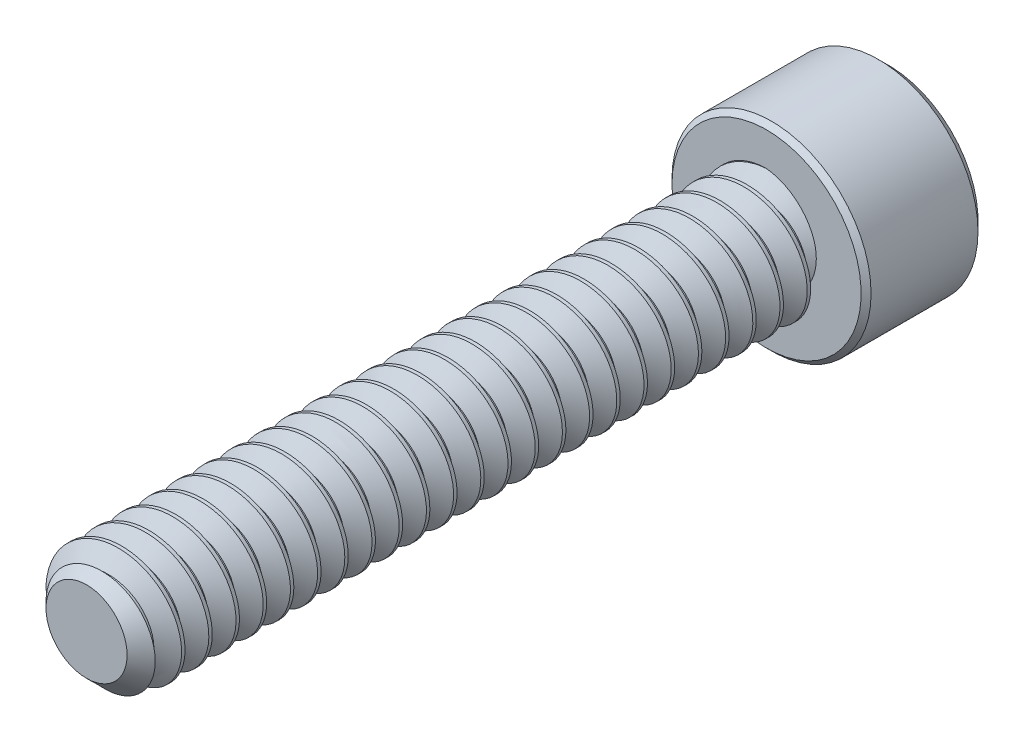
SolidWorks part; units mm, degrees
ref_plane "Front Plane" through (0, 0, 0) normal (0, 0, 1) x (1, 0, 0)
ref_plane "Top Plane" through (0, 0, 0) normal (0, 1, 0) x (1, 0, 0)
ref_plane "Right Plane" through (0, 0, 0) normal (1, 0, 0) x (0, 0, -1)
sketch "Sketch0" plane through (0, 0, 0) normal (1, 0, 0) x (0, 0, -1)
  line L0 (0, 0) -> (15.875, 0) construction
  point P2 (18.7198, 0)
  point P4 (0, 0)
  dimension "D1" = 15.875
  dimension "D2" = 2.8448
  dimension "Min Thread" = 0
sketch "Sketch1" plane through (0, 0, 0) normal (0, 0, 1) x (1, 0, 0)
  circle A0 centre (0, 0) radius 1.4224
  dimension "OD" = 2.8448
extrude "Extrude1" add sketch "Sketch1" against normal blind 15.875
sketch "Sketch2" plane through (0, 0, 0) normal (0, 0, 1) x (1, 0, 0)
  circle A0 centre (0, 0) radius 1.4224 construction
  circle A1 centre (0, 0) radius 1.4224
curve "Helix/Spiral1" pitch 0.635 height 16.51 turns 26 parameters "pitch"=0.635
chamfer "Chamfer3" distance 0.4763 angle 45 1 edges at (1.4224, 0, 0)
sketch "Sketch3" plane through (0, 0, 0) normal (1, 0, 0) x (0, 0, -1)
  line L0 (-0.5556, 1.4224) -> (-0.3175, 1.01)
  line L1 (-0.3175, 1.01) -> (-0.2381, 1.01)
  line L2 (-0.2381, 1.01) -> (0, 1.4224)
  line L3 (-0.5556, 1.4224) -> (0, 1.4224)
  line L4 (-0.2778, 1.4224) -> (-0.2778, 1.01) construction
  line L5 (-0.4366, 1.2162) -> (-0.1191, 1.2162) construction
  line L6 (0, 1.4224) -> (0, -1.4224) construction
  dimension "D1" = 0.0794
  dimension "D2" = 0.3175
  dimension "D3" = 60
sweep "Cut-Sweep1" cut profiles "Sketch3" path "Helix/Spiral1"
sketch "Sketch5" plane through (0, 0, 0) normal (1, 0, 0) x (0, 0, -1)
  line L0 (15.875, -1.0232) -> (15.875, 1.0149) construction
  line L1 (15.875, 1.4224) -> (0, 1.4224)
  line L2 (15.875, 1.4224) -> (15.875, 0)
  line L3 (15.875, 0) -> (-0.5177, 0)
  line L4 (0, 0) -> (15.875, 0) construction
  line L5 (0, 1.4224) -> (-0.5177, 0)
  line L6 (0, 0) -> (18.415, 0) construction
  dimension "D1" = 70
  dimension "D3" = 2.54
revolve "partially thread" [suppressed] add sketch "Sketch5" angle 360 about L6
sketch "Sketch6" plane through (0, 0, -15.875) normal (0, 0, -1) x (-1, 0, 0)
  circle A0 centre (0, 0) radius 2.3241
  dimension "head dia" = 4.6482
extrude "Extrude2" add sketch "Sketch6" along normal blind 2.8448
sketch "Sketch7" plane through (0, 0, -18.7198) normal (0, 0, -1) x (-1, 0, 0)
  line L1 (0, 1.3748) -> (-1.1906, 0.6874)
  line L2 (-1.1906, 0.6874) -> (-1.1906, -0.6874)
  line L3 (-1.1906, -0.6874) -> (0, -1.3748)
  line L4 (0, -1.3748) -> (1.1906, -0.6874)
  line L5 (1.1906, -0.6874) -> (1.1906, 0.6874)
  line L6 (1.1906, 0.6874) -> (0, 1.3748)
  circle A0 centre (0, 0) radius 1.1906 construction
  dimension "hex dia" = 2.3813
extrude "Cut-Extrude1" cut sketch "Sketch7" against normal blind 1.7859
sketch "Sketch8" plane through (0, 0, -18.7198) normal (0, 0, -1) x (-1, 0, 0)
  circle A0 centre (0, 0) radius 1.3748
extrude "Cut-Extrude2" cut sketch "Sketch8" against normal through all draft 45
chamfer "Chamfer1" distance 0.2324 angle 45 1 edges at (-2.3241, 0, -18.7198)
chamfer "Chamfer2" distance 0.1162 angle 45 1 edges at (-2.3241, 0, -15.875)
sketch "Sketch9" plane through (0, 0, 0) normal (1, 0, 0) x (0, 0, -1)
  line L0 (0, 1.4224) -> (0, -1.4224) construction
  line L1 (1.5875, 1.4224) -> (1.5875, -1.4224) construction
  line L2 (18.7198, 2.3241) -> (18.7198, -2.3241) construction
  line L3 (15.875, 2.3241) -> (15.875, -2.3241) construction
  line L4 (15.875, 2.2079) -> (15.875, -2.2079) construction
  line L5 (18.7198, -2.0917) -> (18.7198, 2.0917) construction
  line L6 (15.875, -2.3241) -> (15.875, 2.3241) construction
  line L7 (0, 0.9462) -> (0, -0.9462) construction
  line L8 (-0.5556, 1.4224) -> (0, 1.4224) construction
  line L9 (1.5875, 0) -> (0, 0) construction
  dimension "D1" = 1.5875
equation "\"D3@Helix/Spiral1\" = \"screw length@Extrude1\"+\"pitch@Helix/Spiral1\""
equation "\"D1@Sketch3\" = \"pitch@Helix/Spiral1\"*.125"
equation "\"D2@Sketch3\" = \"pitch@Helix/Spiral1\"*.5"
equation "\"D1@Cut-Extrude1\" = \"hex dia@Sketch7\"*.75"
equation "\"D1@Chamfer1\" = \"head dia@Sketch6\"*.05"
equation "\"D1@Sketch9\" = \"pitch@Helix/Spiral1\"*2.50"
equation "\"D1@Chamfer2\" = \"D1@Chamfer1\"/2"
equation "\"D1@Chamfer3\" = \"pitch@Helix/Spiral1\"*.750"
equation "\"D1@Sketch0\" = \"screw length@Extrude1\""
equation "\"D2@Sketch0\" = \"head depth@Extrude2\""
